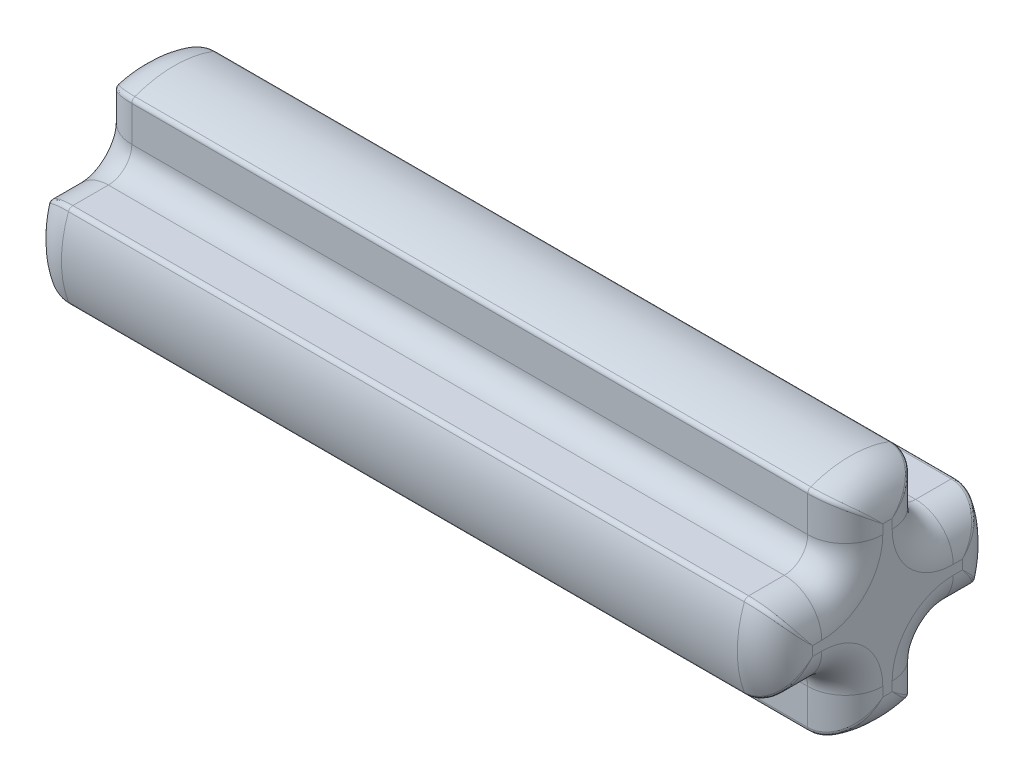
SolidWorks part; units mm, degrees
material "PET"
ref_plane "Alzado" through (0, 0, 0) normal (0, 0, 1) x (1, 0, 0)
ref_plane "Planta" through (0, 0, 0) normal (0, 1, 0) x (1, 0, 0)
ref_plane "Vista lateral" through (0, 0, 0) normal (1, 0, 0) x (0, 0, -1)
sketch "Croquis1" plane through (0, 0, 0) normal (1, 0, 0) x (0, 0, -1)
  line B0 (-1.4, 0.9) -> (-2.2249, 0.9)
  line B1 (0.9, -2.2249) -> (0.9, -1.4)
  line B2 (-0.9, -2.2249) -> (-0.9, -1.4)
  line B3 (2.2249, 0.9) -> (1.4, 0.9)
  line B4 (2.2249, -0.9) -> (1.4, -0.9)
  line B5 (-0.9, 1.4) -> (-0.9, 2.2249)
  line B6 (0.9, 1.4) -> (0.9, 2.2249)
  line B7 (-1.4, -0.9) -> (-2.2249, -0.9)
  arc B8 (-2.2249, 0.9) -> (-2.2249, -0.9) centre (0, 0) ccw
  arc B9 (-1.4, -0.9) -> (-0.9, -1.4) centre (-1.4, -1.4) cw
  arc B10 (0.9, -1.4) -> (1.4, -0.9) centre (1.4, -1.4) cw
  arc B11 (1.4, 0.9) -> (0.9, 1.4) centre (1.4, 1.4) cw
  arc B12 (-0.9, 1.4) -> (-1.4, 0.9) centre (-1.4, 1.4) cw
  arc B13 (0.9, 2.2249) -> (-0.9, 2.2249) centre (0, 0) ccw
  arc B14 (2.2249, -0.9) -> (2.2249, 0.9) centre (0, 0) ccw
  arc B15 (-0.9, -2.2249) -> (0.9, -2.2249) centre (0, 0) ccw
sketch_block_instance "Axle Section Block-1"
sketch_block "Axle Section Block" parameters "D1"=4.8, "D3"=0.5, "D2"=1.8
extrude "Saliente-Extruir1" add sketch "Croquis1" along normal blind 16
fillet "Redondeo1" radius 0.1 8 edges at (8, -2.2249, -0.9) (8, -0.9, -2.2249) (8, 0.9, -2.2249) (8, 2.2249, -0.9) (8, 2.2249, 0.9) (8, -2.2249, 0.9) (8, -0.9, 2.2249) (8, 0.9, 2.2249)
fillet "Redondeo2" radius 0.8 48 edges at (0, 1.7782, 0.9) (0, 1.0464, 1.0464) (0, 0.9, 1.7782) (0, 0, 2.4) (0, -0.9, 1.7782) (0, -1.0464, 1.0464) (0, -1.7782, 0.9) (0, -2.4, 0) (0, -1.7782, -0.9) (0, -1.0464, -1.0464) (0, -0.9, -1.7782) (0, 0, -2.4) (0, 0.9, -1.7782) (0, 1.0464, -1.0464) (0, 1.7782, -0.9) (0, 2.4, 0) (16, 1.7782, -0.9) (16, 1.0464, -1.0464) (16, 0.9, -1.7782) (16, 0, -2.4) (16, -0.9, -1.7782) (16, -1.0464, -1.0464) (16, -1.7782, -0.9) (16, -2.4, 0) (16, -1.7782, 0.9) (16, -1.0464, 1.0464) (16, -0.9, 1.7782) (16, 0, 2.4) (16, 0.9, 1.7782) (16, 1.0464, 1.0464) (16, 1.7782, 0.9) (16, 2.4, 0) (0, -0.8821, -2.2135) (0, 0.8821, -2.2135) (0, 2.2135, -0.8821) (0, 2.2135, 0.8821) (0, 0.8821, 2.2135) (0, -0.8821, 2.2135) (0, -2.2135, 0.8821) (0, -2.2135, -0.8821) (16, -2.2135, 0.8821) (16, -0.8821, 2.2135) (16, 0.8821, 2.2135) (16, 2.2135, 0.8821) (16, 2.2135, -0.8821) (16, 0.8821, -2.2135) (16, -0.8821, -2.2135) (16, -2.2135, -0.8821)
